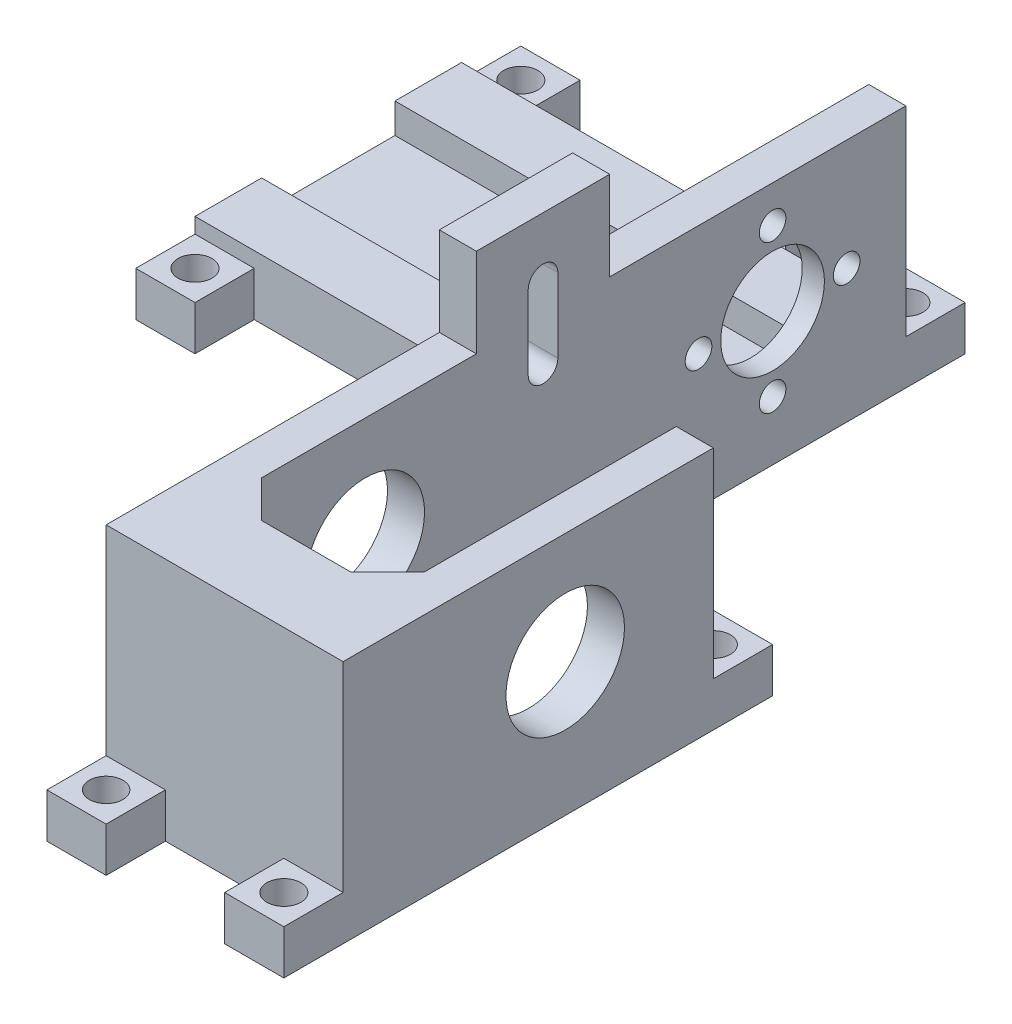
SolidWorks part; units mm, degrees
ref_plane "Plan de face" through (0, 0, 0) normal (0, 0, 1) x (1, 0, 0)
ref_plane "Plan de dessus" through (0, 0, 0) normal (0, 1, 0) x (1, 0, 0)
ref_plane "Plan de droite" through (0, 0, 0) normal (1, 0, 0) x (0, 0, -1)
sketch "Esquisse1" plane through (0, 0, 0) normal (0, 1, 0) x (1, 0, 0)
  line L0 (0, 0) -> (17, 0)
  line L1 (0, 0) -> (-15, 0)
  line L2 (-15, 0) -> (-15, 50)
  line L3 (-15, 50) -> (-10, 50)
  line L4 (-10, 50) -> (-10, 6)
  line L5 (17, 0) -> (17, 50)
  line L6 (17, 50) -> (12, 50)
  line L7 (12, 50) -> (12, 6)
  line L8 (12, 6) -> (-10, 6)
  line L9 (-15, 0) -> (-15, 103)
  line L10 (-10, 73) -> (-70, 73)
  line L11 (-70, 73) -> (-70, 103)
  line L12 (-70, 103) -> (-10, 103)
  line L17 (-10, 50) -> (-10, 103) construction
  line L18 (-10, 103) -> (-15, 103)
  line L19 (-10, 103) -> (-10, 73)
  line L20 (-10, 73) -> (-10, 50)
extrude "Boss.-Extru.1" add sketch "Esquisse1" along normal blind 45 contours L20 L9 L3 | L9 | L7 L8 L4 L3 L2 L1 L0 L5 L6 region at (-7.5, 0, -0.5936) region at (-12.5, 0, -61.5) region at (-12.5, 0, -88)
sketch "Esquisse2" plane through (17, 0, 0) normal (1, 0, 0) x (0, 0, -1)
  line L0 (0, 0) -> (30, 0) construction
  line L2 (0, 0) -> (103, 0) construction
  line L3 (30, 0) -> (30, 18) construction
  circle A0 centre (30, 18) radius 8
extrude "Enlèv. mat.-Extru.1" cut sketch "Esquisse2" against normal blind 50
sketch "Esquisse3" plane through (-15, 0, 0) normal (-1, 0, 0) x (0, 0, 1)
  line L0 (0, 0) -> (-54, 0) construction
  line L1 (0, 0) -> (-103, 0) construction
  line L2 (-54, 0) -> (-54, 45) construction
  line L3 (0, 45) -> (-103, 45) construction
  line L4 (-54, 45) -> (-54, 37) construction
  line L5 (-52, 37) -> (-52, 27)
  line L6 (-52, 27) -> (-56, 27) construction
  line L7 (-56, 27) -> (-56, 37)
  circle A0 centre (-54, 37) radius 2
  circle A1 centre (-54, 27) radius 2
extrude "Enlèv. mat.-Extru.2" cut sketch "Esquisse3" against normal blind 50 contours A1 L5 A0 L7 | A0 | A1 region at (-15, 37, -54) region at (-15, 32, -54) region at (-15, 27, -54)
sketch "Esquisse4" plane through (-10, 0, 0) normal (1, 0, 0) x (0, 0, -1)
  line L0 (103, 0) -> (67, 0)
  line L1 (103, 0) -> (6, 0) construction
  line L2 (85, 18) -> (85, 8) construction
  line L3 (85, 18) -> (85, 28) construction
  line L4 (85, 28) -> (85, 18) construction
  line L5 (85, 18) -> (75, 18) construction
  line L6 (67, 0) -> (76, 0) construction
  line L7 (85, 18) -> (95, 18) construction
  line L8 (103, 0) -> (94, 0) construction
  line L9 (94, 0) -> (94, 8.0723)
  line L10 (94, 8.0723) -> (103, 8.0723)
  line L11 (103, 45) -> (103, 0) construction
  line L12 (94, 0) -> (85, 0) construction
  line L13 (76, 8.0723) -> (76, 0)
  line L14 (76, 8.0723) -> (67, 8.0723)
  line L15 (67, 8.0723) -> (67, 0)
  line L16 (103, 8.0723) -> (103, 0)
  line L17 (103, 8.0723) -> (103, 0)
  line L18 (94, 0) -> (103, 0)
  line L19 (76, 0) -> (76, 4)
  line L20 (76, 4) -> (94, 4.0361)
  line L21 (94, 4.0361) -> (94, 0)
  circle A0 centre (85, 18) radius 13.4
  circle A1 centre (75, 18) radius 1.8
  circle A2 centre (85, 8) radius 1.8
  circle A3 centre (95, 18) radius 1.8
  circle A4 centre (85, 28) radius 1.8
  circle A5 centre (85, 18) radius 7
  line M8 (6, 0) -> (103, 0)
  line M9 (103, 0) -> (103, 45)
extrude "Enlèv. mat.-Extru.3" cut sketch "Esquisse4" against normal blind 5 contours A2 | A3 | A1 | A4 | A5 region at (-10, 18, -75) region at (-10, 8, -85) region at (-10, 18, -95)
extrude "Boss.-Extru.2" add sketch "Esquisse4<4>" against normal blind 60 contours L10 L9 L0 M9 | L14 L15 L13 M8 | L20 L13 L0 L9 region at (-10, 4.0361, -98.5) region at (-10, 2.009, -85.0135) region at (-10, 4.0361, -71.5)
sketch "Esquisse4<4>" plane through (-10, 0, 0) normal (1, 0, 0) x (0, 0, -1) same geometry as "Esquisse4"
sketch "Esquisse6" plane through (0, 0, 0) normal (0, -1, 0) x (1, 0, 0)
  line L0 (-10, -6) -> (12, -6)
  line L1 (12, -6) -> (12, -16)
  line L2 (12, -50) -> (12, -6) construction
  line L3 (-10, -6) -> (-10, -16)
  line L4 (-10, -103) -> (-10, -6) construction
  line L5 (-10, -6) -> (-5, -6)
  line L6 (-5, -6) -> (-5, -11) construction
  line L7 (12, -6) -> (7, -6)
  line L8 (7, -6) -> (7, -11) construction
  line L9 (7, -11) -> (-5, -11)
  line L10 (-10, -16) -> (-5, -11)
  line L11 (7, -11) -> (12, -16)
  line M9 (-10, -103) -> (-10, -6)
  line M10 (-10, -6) -> (12, -6)
  line M11 (12, -6) -> (12, -50)
extrude "Boss.-Extru.3" add sketch "Esquisse6" against normal blind 45 contours L9 L11 L0 L10 M11 M10 M9 region at (1, 0, -9.2716)
sketch "Esquisse11" plane through (0, 0, 0) normal (0, -1, 0) x (1, 0, 0)
  line L0 (17, 0) -> (17, 8)
  line L1 (17, 8) -> (9, 8)
  line L2 (9, 8) -> (9, 0)
  line L3 (17, 0) -> (-15, 0) construction
  line L4 (9, 0) -> (17, 0)
  line L5 (-15, 0) -> (-15, 8)
  line L6 (-15, 8) -> (-7, 8)
  line L7 (-7, 8) -> (-7, 0)
  line L8 (-7, 0) -> (-15, 0)
  line L9 (-70, -67) -> (-70, -59)
  line L10 (-70, -59) -> (-62, -59)
  line L11 (-62, -59) -> (-62, -67)
  line L12 (-70, -67) -> (-15, -67) construction
  line L13 (-10, -103) -> (-10, -111)
  line L14 (-10, -111) -> (-18, -111)
  line L15 (-18, -111) -> (-18, -103)
  line L16 (-70, -103) -> (-10, -103) construction
  line L17 (-70, -103) -> (-70, -111)
  line L18 (-70, -111) -> (-62, -111)
  line L19 (-62, -111) -> (-62, -103)
  line L20 (-62, -103) -> (-70, -103)
  line L21 (-18, -103) -> (-10, -103)
  line L22 (-62, -67) -> (-70, -67)
  line L23 (-70, -59) -> (-62, -67) construction
  line L24 (-62, -59) -> (-70, -67) construction
  line L25 (-70, -103) -> (-62, -111) construction
  line L26 (-62, -103) -> (-70, -111) construction
  line L27 (-18, -111) -> (-10, -103) construction
  line L28 (-18, -103) -> (-10, -111) construction
  line L29 (-15, 8) -> (-7, 0) construction
  line L30 (-15, 0) -> (-7, 8) construction
  line L31 (9, 8) -> (17, 0) construction
  line L32 (17, 8) -> (9, 0) construction
  line L37 (-23, -103) -> (-23, -111)
  line L45 (-23, -111) -> (-31, -111)
  line L47 (17, -50) -> (17, -58)
  line L48 (17, -58) -> (9, -58)
  line L49 (9, -58) -> (9, -46)
  line L50 (9, -46) -> (12, -46)
  line L51 (12, -50) -> (12, -16) construction
  line L52 (12, -46) -> (12, -50) construction
  line L53 (17, -50) -> (12, -50) construction
  line L54 (12, -50) -> (9, -50) construction
  line L55 (17, -58) -> (9, -50) construction
  line L56 (9, -50) -> (9, -58) construction
  line L57 (17, -50) -> (9, -58) construction
  line L58 (-15, -67) -> (-15, -103) construction
  line L59 (-15, -103) -> (-23, -103)
  line L60 (-31, -111) -> (-31, -103)
  line L61 (-31, -103) -> (-23, -103)
  line L62 (-31, -103) -> (-23, -111) construction
  line L63 (-23, -103) -> (-31, -111) construction
  circle A2 centre (-11, 4) radius 2.268
  circle A3 centre (13, 4) radius 2.3
  circle A4 centre (-66, -63) radius 2.3
  circle A5 centre (-66, -107) radius 2.3
  circle A6 centre (-14, -107) radius 2.3
  circle A8 centre (13, -54) radius 2.3
  circle A9 centre (-27, -107) radius 2.3
  line M9 (-15, -67) -> (-70, -67)
  line M11 (-70, -103) -> (-10, -103)
  line M16 (12, -16) -> (12, -50)
  line M17 (12, -50) -> (17, -50)
  line M18 (17, -50) -> (17, 0)
  line M19 (17, 0) -> (-15, 0)
extrude "Boss.-Extru.6" add sketch "Esquisse11" against normal blind 6 contours L11 L10 L9 A4 M9 | L18 L19 L17 A5 M11 | L7 L6 L5 A2 M19 | L1 L2 L0 A3 M19 | L48 M17 M16 | L48 L49 L47 M18 | L14 L15 L21 L13 | A6 | L37 L45 L60 L61 | A9 region at (13, 0, 0.1131) region at (-11, 0, 0.1131) region at (16.8558, 0, -54) region at (-69.8869, 0, -63) region at (-62.1131, 0, -107)
sketch "Esquisse12" plane through (-15, 0, 0) normal (-1, 0, 0) x (0, 0, 1)
  line L0 (0, 45) -> (0, 33)
  line L1 (0, 45) -> (0, 6) construction
  line L2 (0, 33) -> (-45, 33)
  line L3 (-45, 33) -> (-45, 45)
  line L4 (0, 45) -> (-103, 45) construction
  line L8 (-103, 45) -> (-103, 8.0723) construction
  line L9 (-103, 33) -> (-103, 45)
  line L10 (-103, 45) -> (0, 45)
  line L11 (-45, 45) -> (-63, 45)
  line L12 (-63, 45) -> (-63, 33)
  line L13 (-103, 33) -> (-63, 33)
  line M9 (0, 6) -> (0, 45)
  line M10 (0, 45) -> (-103, 45)
  line M11 (-103, 45) -> (-103, 8.0723)
extrude "Enlèv. mat.-Extru.5" cut sketch "Esquisse12" against normal blind 50 contours L13 L12 L10 M11 | L3 L2 M9 M10 region at (-15, 39, -83) region at (-15, 39, -22.5)
sketch "Esquisse13" plane through (17, 0, 0) normal (1, 0, 0) x (0, 0, -1)
  line L0 (45, 33) -> (50, 33)
  line L1 (50, 45) -> (50, 6) construction
  line L2 (50, 33) -> (50, 45)
  line L3 (50, 45) -> (45, 45)
  line L4 (45, 45) -> (45, 33)
extrude "Enlèv. mat.-Extru.6" cut sketch "Esquisse13" against normal blind 20
sketch "Esquisse24" plane through (-10, 0, 0) normal (1, 0, 0) x (0, 0, -1)
  circle A0 centre (85, 18) radius 13.4
sketch "Esquisse25" plane through (-15, 0, 0) normal (-1, 0, 0) x (0, 0, 1)
  circle A0 centre (-85, 18) radius 13.4
extrude "Enlèv. mat.-Extru.8" cut sketch "Esquisse25" against normal blind 2
